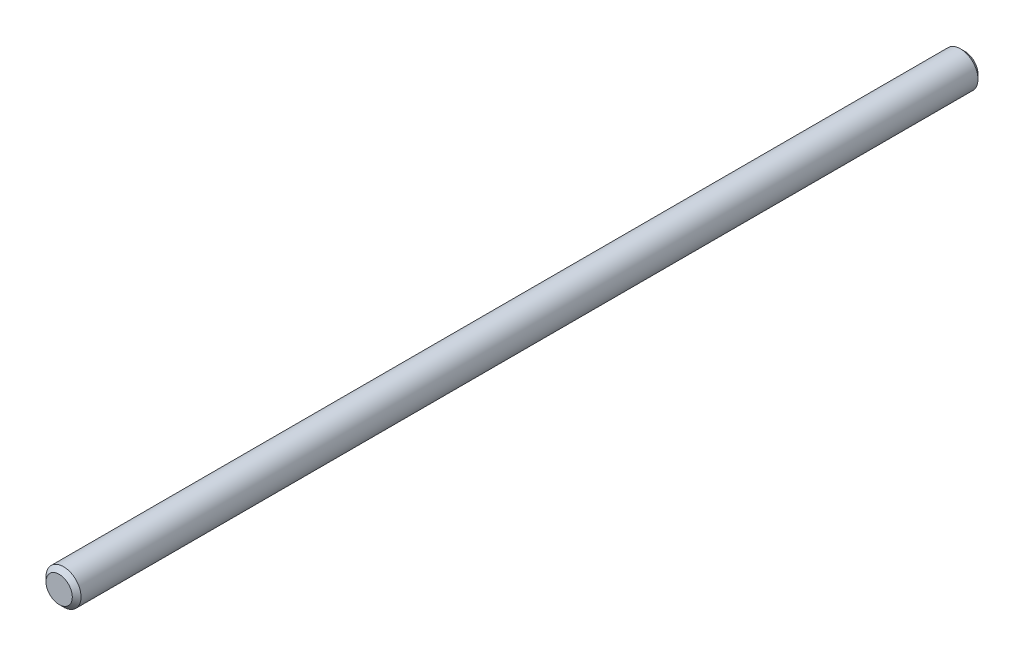
SolidWorks part; units mm, degrees
material "Galvanized Steel"
ref_plane "Front" through (0, 0, 0) normal (0, 0, 1) x (1, 0, 0)
ref_plane "Top" through (0, 0, 0) normal (0, 1, 0) x (1, 0, 0)
ref_plane "Right" through (0, 0, 0) normal (1, 0, 0) x (0, 0, -1)
ref_axis "Axis1" through (-84.4107, 0, 0) along (1, 0, 0)
ref_axis "Axis2" through (0, 64.3378, 0) along (0, -1, 0)
ref_axis "Axis3" through (0, 0, -102.329) along (0, 0, 1)
sketch "Sketch1" plane through (0, 0, 0) normal (0, 0, 1) x (1, 0, 0)
  circle A0 centre (0, 0) radius 6
  dimension "D1" = 12
extrude "Boss-Extrude1" add sketch "Sketch1" along normal blind 310
chamfer "Chamfer1" distance 1.5 angle 45 2 edges at (6, 0, 310) (6, 0, 0)
